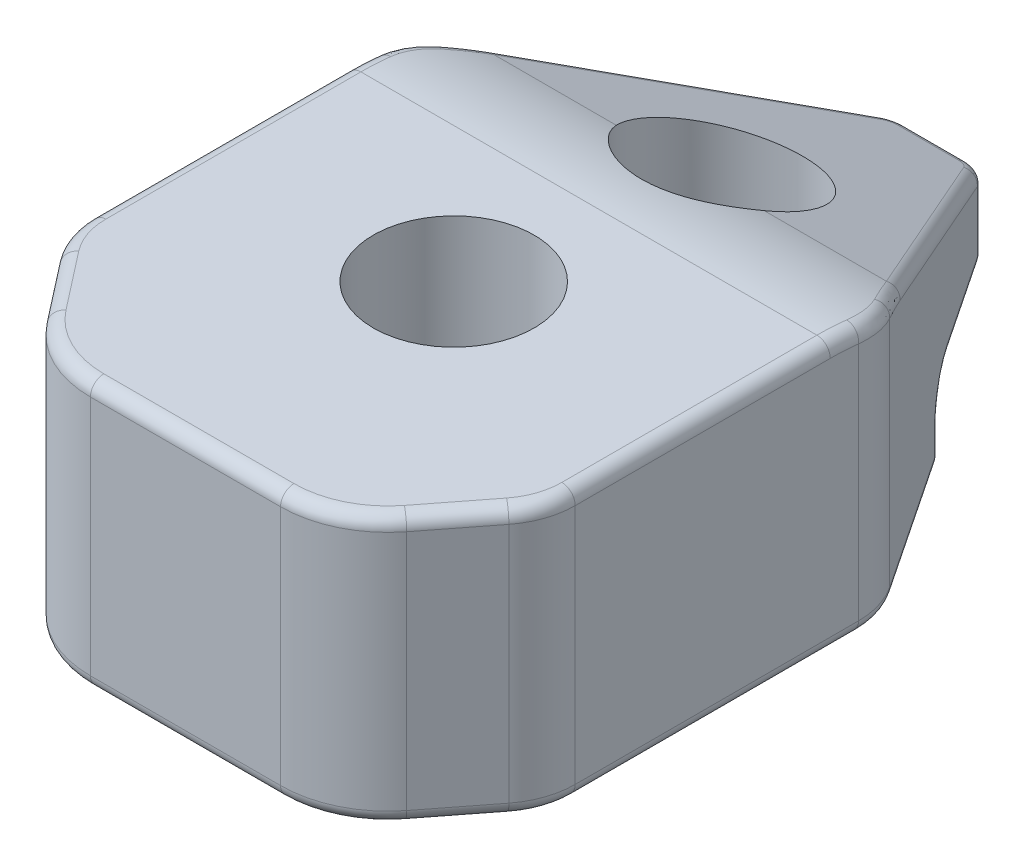
SolidWorks part; units mm, degrees
material "ｼﾘｺﾝ ｺﾞﾑ"
ref_plane "正面" through (0, 0, 0) normal (0, 0, 1) x (1, 0, 0)
ref_plane "平面" through (0, 0, 0) normal (0, 1, 0) x (1, 0, 0)
ref_plane "右側面" through (0, 0, 0) normal (1, 0, 0) x (0, 0, -1)
sketch "ｽｹｯﾁ1" plane through (0, 0, 0) normal (0, 1, 0) x (1, 0, 0)
  line L0 (0, 0) -> (18, 0)
  line L1 (18, 0) -> (18, 23)
  line L2 (18, 23) -> (0, 23)
  line L3 (0, 23) -> (0, 0)
  line L4 (9, 0) -> (14.5, 0)
  line L5 (14.5, 0) -> (3.5, 0)
  line L6 (9, 0) -> (9, 4.5)
  line L7 (9, 4.5) -> (18, 4.5)
  line L8 (18, 4.5) -> (14.5, 0)
  line L9 (9, 4.5) -> (0, 4.5)
  line L10 (0, 4.5) -> (3.5, 0)
  line L11 (9, 23) -> (4, 23)
  line L12 (4, 23) -> (14, 23)
  line L13 (9, 23) -> (9, 17)
  line L14 (9, 17) -> (18, 17)
  line L15 (18, 17) -> (14, 23)
  line L16 (4, 23) -> (0, 17)
extrude "ﾎﾞｽ - 押し出し1" add sketch "ｽｹｯﾁ1" along normal blind 2.5 contours L2 L16 L3 L9 L7 L1 L14 L13 | L14 L15 L2 L13 | L8 L7 L6 L0 | L9 L10 L0 L6 region at (5.3046, 0, -2.431) region at (8.4345, 0, -12.1601) region at (12.6954, 0, -2.431) region at (12.5952, 0, -19.7143)
sketch "ｽｹｯﾁ2" plane through (0, 2.5, 0) normal (0, 1, 0) x (1, 0, 0)
  line L0 (18, 17) -> (0, 17)
  line L1 (0, 17) -> (0, 4.5)
  line L2 (0, 4.5) -> (3.5, 0)
  line L3 (3.5, 0) -> (14.5, 0)
  line L4 (14.5, 0) -> (18, 4.5)
  line L5 (18, 4.5) -> (18, 17)
extrude "ﾎﾞｽ - 押し出し2" add sketch "ｽｹｯﾁ2" along normal blind 7.5
sketch "ｽｹｯﾁ3" plane through (0, 2.5, 0) normal (0, 1, 0) x (1, 0, 0)
  line L0 (4, 23) -> (9, 23)
  line L1 (14, 23) -> (4, 23) construction
  line L2 (9, 23) -> (9, 28)
  line L5 (0, 17) -> (4, 23)
  line L6 (4, 23) -> (7.3333, 28)
  line L7 (18, 17) -> (14, 23)
  line L8 (14, 23) -> (10.6667, 28)
  line L9 (10.6667, 28) -> (7.3333, 28)
  line L10 (10.6667, 28) -> (7.3333, 28)
  line M1 (0, 17) -> (18, 17)
  line M2 (18, 17) -> (14, 23)
  line M3 (14, 23) -> (4, 23)
  line M4 (4, 23) -> (0, 17)
extrude "ﾎﾞｽ - 押し出し3" add sketch "ｽｹｯﾁ3" along normal blind 7.5 contours L2 L9 L6 M3 | L8 L9 L2 M3 | M4 M1 M2 M3 region at (7.1944, 2.5, -25.0833) region at (9, 2.5, -19.7143) region at (10.8056, 2.5, -25.0833)
chamfer "面取り2" distance 11 angle 22.2 1 edges at (9, 10, -28) first distance on face at (9, 10, -12.375)
fillet "ﾌｨﾚｯﾄ1" radius 3 4 edges at (18, 5, -4.5) (0, 5, -4.5) (0, 5, -17) (18, 5, -17)
fillet "ﾌｨﾚｯﾄ2" radius 4 2 edges at (14.5, 5, 0) (3.5, 5, 0)
fillet "ﾌｨﾚｯﾄ3" radius 1 1 edges at (9, 2.5, -23)
fillet "ﾌｨﾚｯﾄ4" radius 0.5 1 edges at (9, 0, -23)
fillet "ﾌｨﾚｯﾄ5" radius 1 2 edges at (7.3333, 4.0055, -28) (10.6667, 4.0055, -28)
fillet "ﾌｨﾚｯﾄ6" radius 10 1 edges at (9, 10, -17)
sketch "ｽｹｯﾁ5" plane through (0, 0, 0) normal (0, -1, 0) x (1, 0, 0)
  line L0 (9, 0) -> (9, -10)
  line L1 (5.4563, 0) -> (12.5437, 0) construction
  line L2 (9, -10) -> (9, -20)
  circle A0 centre (9, -10) radius 1.5
  circle A1 centre (9, -20) radius 1.5
extrude "ｶｯﾄ - 押し出し1" cut sketch "ｽｹｯﾁ5" against normal through all contours A1 | L0 A0 L2 | L2 A0 L0 region at (9.6366, 0, -10) region at (10.0307, 0, -18.9693) region at (8.3634, 0, -10)
sketch "ｽｹｯﾁ6" plane through (0, 10, 0) normal (0, 1, 0) x (1, 0, 0)
  circle A0 centre (9, 10) radius 3
  circle A1 centre (9, 20) radius 3
  circle A2 centre (9, 10) radius 1.5
  circle A3 centre (9, 20) radius 1.5
extrude "ｶｯﾄ - 押し出し2" cut sketch "ｽｹｯﾁ6" against normal blind 5.5
fillet "ﾌｨﾚｯﾄ7" radius 0.5 20 edges at (17.1392, 9.456, -18.2913) (17.9045, 9.8359, -16.8425) (18, 9.9861, -15.5656) (18, 10, -10.2837) (17.8376, 10, -4.5557) (16.5346, 10, -2.6159) (14.3011, 10, -0.4067) (3.6989, 10, -0.4067) (9, 10, 0) (1.4654, 10, -2.6159) (0.1624, 10, -4.5557) (0, 10, -10.2837) (0, 9.9861, -15.5656) (0.1663, 9.79, -17.0766) (0.8608, 9.456, -18.2913) (4.1237, 7.4757, -23.1856) (7.3967, 5.5593, -27.8817) (9, 5.511, -28) (10.6033, 5.5593, -27.8817) (13.8763, 7.4757, -23.1856)
fillet "ﾌｨﾚｯﾄ8" radius 0.5 24 edges at (7.3967, 2.5, -27.8817) (5.8516, 2.5, -25.7774) (4.1953, 2.2071, -23.2929) (4, 1, -23) (3.9024, 0.1464, -22.8536) (2.0853, 0, -20.1279) (0.1287, 0, -16.961) (0, 0, -10.8105) (0.1624, 0, -4.5557) (1.4654, 0, -2.6159) (3.6989, 0, -0.4067) (9, 0, 0) (14.3011, 0, -0.4067) (16.5346, 0, -2.6159) (17.8376, 0, -4.5557) (18, 0, -10.8105) (17.8713, 0, -16.961) (15.9147, 0, -20.1279) (14.0976, 0.1464, -22.8536) (14, 1, -23) (13.8047, 2.2071, -23.2929) (12.1484, 2.5, -25.7774) (9, 2.5, -28) (10.6033, 2.5, -27.8817)
